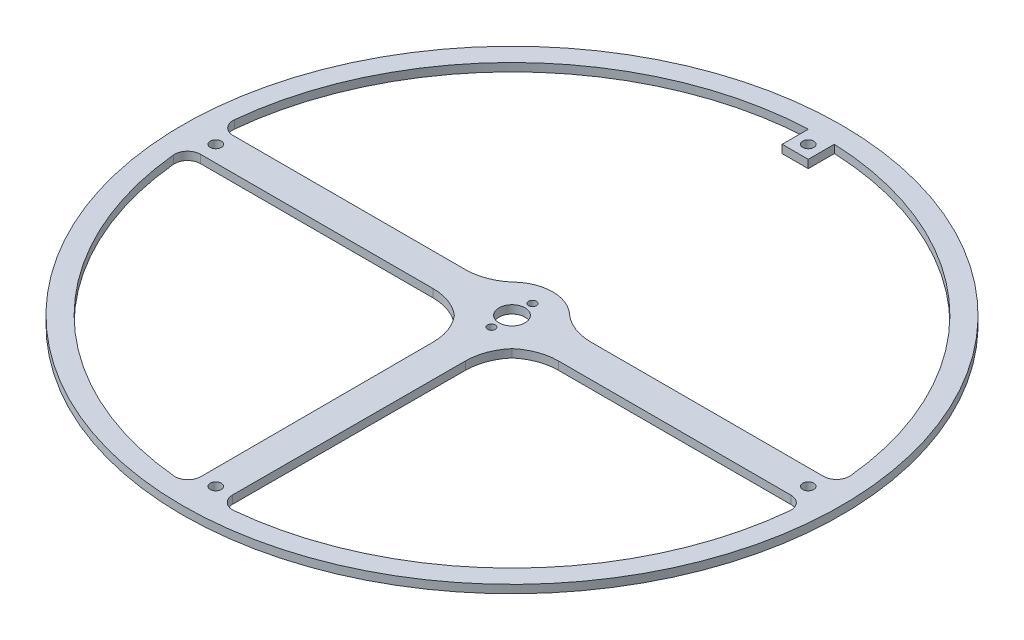
SolidWorks part; units mm, degrees
ref_plane "Front Plane" through (0, 0, 0) normal (0, 0, 1) x (1, 0, 0)
ref_plane "Top Plane" through (0, 0, 0) normal (0, 1, 0) x (1, 0, 0)
ref_plane "Right Plane" through (0, 0, 0) normal (1, 0, 0) x (0, 0, -1)
sketch "Sketch1" plane through (0, 0, 0) normal (0, 1, 0) x (1, 0, 0)
  line L0 (-14.5497, 6.35) -> (-120.6405, 6.35)
  line L1 (120.6405, -6.35) -> (14.5497, -6.35)
  line L3 (120.6405, 6.35) -> (14.5497, 6.35)
  line L12 (6.35, -14.5497) -> (6.171, -120.6498)
  line L13 (-6.35, -14.5497) -> (-6.171, -120.6498)
  line L14 (-14.5497, -6.35) -> (-120.6405, -6.35)
  line L18 (-5.08, 120.7006) -> (-5.08, 110.4973)
  line L19 (-5.08, 110.4973) -> (5.08, 110.4973)
  line L20 (5.08, 120.7006) -> (5.08, 110.4973)
  arc A2 (14.5497, 6.35) -> (-14.5497, 6.35) centre (0, 0) ccw
  arc A3 (-14.5497, -6.35) -> (-6.35, -14.5497) centre (0, 0) ccw
  arc A4 (6.35, -14.5497) -> (14.5497, -6.35) centre (0, 0) ccw
  arc A5 (-120.6405, -6.35) -> (-6.171, -120.6498) centre (0, 0) ccw
  arc A6 (6.171, -120.6498) -> (120.6405, -6.35) centre (0, 0) ccw
  arc A7 (120.6405, 6.35) -> (5.08, 120.7006) centre (0, 0) ccw
  arc A8 (-5.08, 120.7006) -> (-120.6405, 6.35) centre (0, 0) ccw
  point P0 (0, 0)
  point P20 (6.0209, 120.6573)
  dimension "D5" = 31.75
sketch "Screw holes" plane through (0, 0, 0) normal (0, 1, 0) x (1, 0, 0)
  circle A0 centre (0, 8) radius 1.5133
  circle A1 centre (0, -8) radius 1.5133
  circle A2 centre (0, 0) radius 5.08
  dimension "D1" = 16
  dimension "D3" = 3.0266
  dimension "D4" = 10.16
  dimension "D2" = 8
sketch "Sketch4" plane through (0, 0, 0) normal (0, 1, 0) x (1, 0, 0)
  circle A0 centre (0, 0) radius 128.5748
extrude "Boss-Extrude1" add sketch "Sketch4" along normal blind 3.175
extrude "Cut-Extrude2" cut sketch "Sketch1" along normal through all
sketch "Sketch5" plane through (0, 0, 0) normal (0, 1, 0) x (1, 0, 0)
  line L0 (5.08, 110.4973) -> (-5.08, 110.4973) construction
  circle A0 centre (0, 115.5773) radius 2.159
  dimension "D1" = 5.08
  dimension "D2" = 115.5773
extrude "Cut-Extrude3" cut sketch "Sketch5" along normal through all
extrude "middle holes" cut sketch "Screw holes" along normal through all
fillet "Filletmiddle" radius 20.32 6 edges at (14.5497, 1.5875, -6.35) (-14.5497, 1.5875, -6.35) (14.5497, 1.5875, 6.35) (6.35, 1.5875, 14.5497) (-14.5497, 1.5875, 6.35) (-6.35, 1.5875, 14.5497)
fillet "Filletsides" radius 5.08 6 edges at (120.6405, 1.5875, 6.35) (120.6405, 1.5875, -6.35) (-6.171, 1.5875, 120.6498) (6.171, 1.5875, 120.6498) (-120.6405, 1.5875, 6.35) (-120.6405, 1.5875, -6.35)
sketch "Sketch6" plane through (0, 0, 0) normal (0, 1, 0) x (1, 0, 0)
  circle A0 centre (-115.5776, 0) radius 2.159
  circle A1 centre (0, -115.5776) radius 2.159
  circle A2 centre (115.5776, 0) radius 2.159
  dimension "D1" = 115.5776
  dimension "D2" = 115.5776
  dimension "D3" = 115.5776
extrude "Cut-Extrude5" cut sketch "Sketch6" along normal through all
